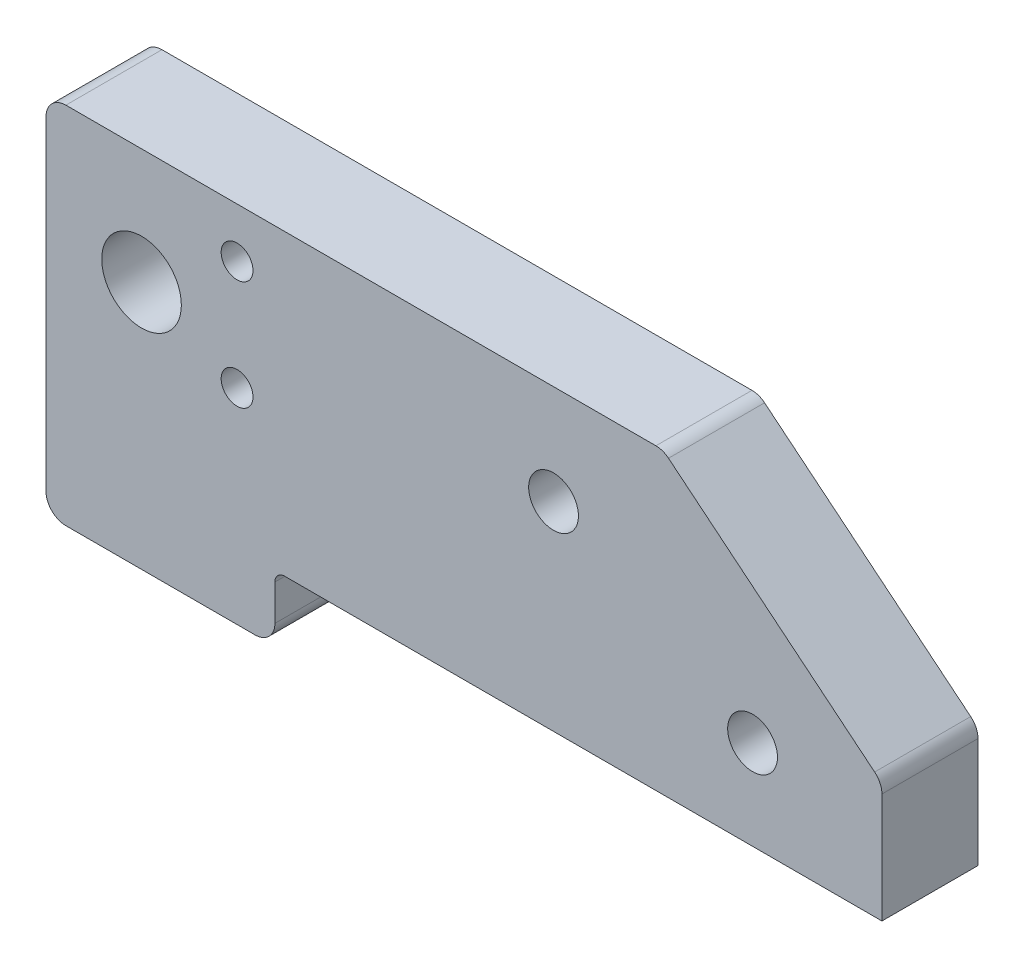
SolidWorks part; units mm, degrees
material "6061-T4 (SS)"
ref_plane "Front" through (0, 0, 0) normal (0, 0, 1) x (1, 0, 0)
ref_plane "Top" through (0, 0, 0) normal (0, 1, 0) x (1, 0, 0)
ref_plane "Right" through (0, 0, 0) normal (1, 0, 0) x (0, 0, -1)
sketch "Sketch1" plane through (0, 0, 0) normal (0, 0, 1) x (1, 0, 0)
  line L0 (-5.5, 10) -> (-5.5, 15) construction
  line L1 (0, 0) -> (-11, 0)
  line L2 (0, 0) -> (0, 15) construction
  line L3 (0, 15) -> (-11, 15)
  line L4 (-11, 0) -> (-11, 15)
  line L5 (-5.5, 10) -> (-11, 10) construction
  line L6 (-5.5, 10) -> (0, 10) construction
  line L7 (0, 15) -> (11, 6)
  line L8 (11, 6) -> (11, 0)
  line L9 (11, 0) -> (0, 0)
  line L10 (-11, 0) -> (-19.5, 0)
  line L11 (-19.5, 0) -> (-19.5, -3.3)
  line L12 (-19.5, -3.3) -> (-31, -3.3)
  line L13 (-31, -3.3) -> (-31, 15)
  line L14 (-31, 15) -> (-11, 15)
  line L16 (-31, 15) -> (-19.5, 15)
  line L17 (-31, 15) -> (-31, 17)
  line L18 (-31, 17) -> (-19.5, 17)
  line L19 (-19.5, 15) -> (-19.5, 17)
  circle A0 centre (-26.2, 9.2) radius 2
  dimension "D3" = 10
  dimension "D12" = 4
  dimension "D1" = 11
  dimension "D2" = 15
  dimension "D4" = 6
  dimension "D5" = 22
  dimension "D7" = 11.5
  dimension "D8" = 3.3
  dimension "D9" = 2
  dimension "D10" = 12.5
  dimension "D11" = 4.8
  dimension "D13" = 20
extrude "Boss-Extrude1" add sketch "Sketch1" along normal blind 4.826 contours L9 L8 L7 L3 L4 L1 region at (-1.2941, 6.7059, 0)
sketch "Sketch_baseplate_mounting" plane through (0, 0, 0) normal (0, -1, 0) x (-1, 0, 0)
  line L0 (11, -4.826) -> (11, 0) construction
  line L1 (4, -2.413) -> (11, -2.413) construction
  line L2 (-11, -2.413) -> (-8, -2.413) construction
  line L4 (-11, -4.826) -> (-11, 0) construction
  dimension "D1" = 7
  dimension "D2" = 3
hole_wizard "M3x0.5 Tapped Hole1" positions "Sketch8" profile "Sketch10" tap size "M3x0.5" standard "ANSI Metric" end condition through all
sketch "Sketch8" plane through (0, 0, 4.826) normal (0, 0, 1) x (1, 0, 0)
  point P0 (-5.5, 10)
sketch "Sketch10" plane through (-5.5, 10, 4.826) normal (1, 0, 0) x (0, -1, 0)
  line L0 (0, 0) -> (0, 4.826)
  line L1 (0, 4.826) -> (1.25, 4.826)
  line L2 (1.25, 4.826) -> (1.25, 0)
  line L5 (1.25, 0) -> (0, 0)
  line L11 (0, -6.35) -> (0, 107.95) construction
  dimension "Thread Major Dia." = 2.5
  dimension "Thru Tap Drill Depth" = 4.826
hole_wizard "Tap Drill for M3x0.5 Tap1" positions "3DSketch1" profile "Sketch5" hole size "M3x0.5" standard "ANSI Metric"
sketch3d "3DSketch1"
  point P0 (-4, 0, 2.413)
  point P3 (8, 0, 2.413)
sketch "Sketch5" plane through (-4, 0, 2.413) normal (1, 0, 0) x (0, 0, -1)
  line L0 (0, 0) -> (0, 5.7511)
  line L1 (0, 5.7511) -> (1.25, 5)
  line L2 (1.25, 5) -> (1.25, 0)
  line L5 (1.25, 0) -> (0, 0)
  line L10 (0, 5.7511) -> (-1.25, 5) construction
  line L11 (0, -6.35) -> (0, 107.95) construction
  dimension "Hole Dia." = 2.5
  dimension "Hole Depth" = 5
  dimension "Drill Angle" = 118
sketch "Sketch_chipper_mounting" plane through (0, 0, 4.826) normal (0, 0, 1) x (1, 0, 0)
  line L0 (4.5, 0) -> (4.5, 4.5) construction
  line L1 (11, 0) -> (-11, 0) construction
  circle A1 centre (-5.5, 10) radius 1.25 construction
  dimension "D1" = 4.5
  dimension "D2" = 10
hole_wizard "M3x0.5 Tapped Hole2" positions "3DSketch2" profile "Sketch7" tap size "M3x0.5" standard "ANSI Metric" end condition through all
sketch3d "3DSketch2"
  point P0 (4.5, 4.5, 4.826)
sketch "Sketch7" plane through (4.5, 4.5, 4.826) normal (1, 0, 0) x (0, -1, 0)
  line L0 (0, 0) -> (0, 4.826)
  line L1 (0, 4.826) -> (1.25, 4.826)
  line L2 (1.25, 4.826) -> (1.25, 0)
  line L5 (1.25, 0) -> (0, 0)
  line L11 (0, -6.35) -> (0, 107.95) construction
  dimension "Thread Major Dia." = 2.5
  dimension "Thru Tap Drill Depth" = 4.826
extrude "Boss-Extrude2" add sketch "Sketch1<3>" along normal up to surface (4.826 mm away) contours L14 L13 L12 L11 L10 L4 region at (-21.2949, 6.3672, 0) up to face at (5.75, 4.5, 4.826)
sketch "Sketch1<3>" plane through (0, 0, 0) normal (0, 0, 1) x (1, 0, 0) same geometry as "Sketch1"
fillet "Fillet1" radius 1 5 edges at (-31, 15, 2.413) (-19.5, -3.3, 2.413) (-31, -3.3, 2.413) (11, 6, 2.413) (0, 15, 2.413)
hole_wizard "M2 Tapped Holes" positions "Sketch11" profile "Sketch12" legacy
sketch "Sketch11" plane through (0, 0, 4.826) normal (0, 0, 1) x (1, 0, 0)
  line L0 (-19.5, 7) -> (-21.4, 7) construction
  line L2 (-21.4, 7) -> (-21.4, -3.3) construction
  line L5 (-21.4, 7) -> (-21.4, 12.5) construction
  line L7 (-27.75, 12.5) -> (-15.05, 12.5) construction
  line L8 (-20.5, -3.3) -> (-30, -3.3) construction
  point P0 (-21.4, 12.5)
  point P2 (-21.4, 7)
  dimension "D1" = 10.3
  dimension "D2" = 1.9
  dimension "D3" = 12.7
  dimension "D4" = 15.8
sketch "Sketch12" plane through (-21.4, 12.5, 4.826) normal (1, 0, 0) x (0, -1, 0)
  line L0 (0, 0) -> (0, 4.825)
  line L1 (0, 4.825) -> (0.8, 4.825)
  line L2 (0.8, 4.825) -> (0.8, 0)
  line L3 (0.8, 0) -> (0, 0)
  line L4 (0, 110) -> (0, -10) construction
  dimension "Diameter" = 1.6
  dimension "Depth" = 4.825
fillet "Fillet2" radius 0.5 1 edges at (-19.5, 0, 2.413)
